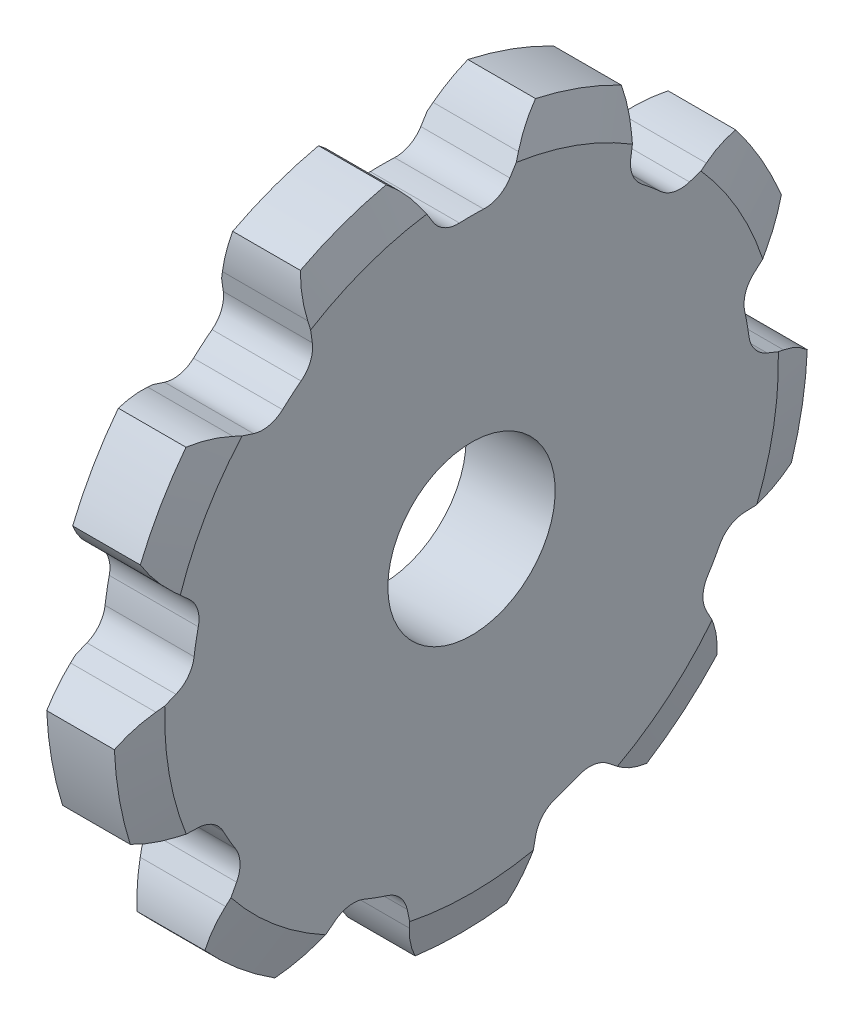
SolidWorks part; units mm, degrees
ref_plane "Plane1" through (0, 0, 0) normal (0, 0, 1) x (1, 0, 0)
ref_plane "Plane2" through (0, 0, 0) normal (0, 1, 0) x (1, 0, 0)
ref_plane "Plane3" through (0, 0, 0) normal (1, 0, 0) x (0, 0, -1)
sketch "Clipboard" plane through (0, 0, 0) normal (0, 1, 0) x (1, 0, 0)
  line L0 (0, 0) -> (65.4527, -10.3667)
  line L1 (-15, 0) -> (100, 0) construction
  line L2 (0, 0) -> (-2.1039, 2.3779)
  line L3 (0, 0) -> (-11.863, 4.5341)
  line L4 (0, 0) -> (8.5297, 1.351)
  line L5 (0, 0) -> (-71.3958, -26.6285)
  line L6 (0, 0) -> (-22.4032, -15.1155)
  line L7 (-2.1039, 2.3779) -> (14.2981, 76.7917)
  line L8 (-76.2, 54.61) -> (-19.7358, 54.61)
  line L9 (-66.6514, 23.5599) -> (-55.7196, 25.8835)
  line L10 (-76.2, 71.12) -> (20.6782, 71.12)
  line L11 (0, 0) -> (-28.448, 0)
  line L12 (-76.2, 101.6) -> (-47.752, 101.6)
  circle A0 centre (0, 0) radius 11.176
  circle A1 centre (0, 0) radius 25.4
  circle A2 centre (0, 0) radius 25.4
  dimension "Num_teeth" = 9
  dimension "Pitch_radius" = 96.8782
  dimension "Width" = 28.448
  dimension "F" = 28.448
  dimension "H" = 11.176
  dimension "Thickness" = 27.0256
sketch "BasProSke" plane through (0, 0, 0) normal (0, 1, 0) x (1, 0, 0)
  line L0 (-10, 0) -> (60, 0) construction
  line L1 (0, 0) -> (0, 93.1564)
  line L2 (0, 0) -> (27.0256, 0)
  line L3 (27.0256, 0) -> (27.0256, 93.1564)
  line L4 (23.7825, 105.2597) -> (3.2431, 105.2597)
  line L5 (0, 93.1564) -> (3.2431, 105.2597)
  line L6 (27.0256, 93.1564) -> (23.7825, 105.2597)
  dimension "Thickness" = 27.0256
  dimension "Diameter" = 210.5195
  dimension "D1" = 15
  dimension "D2" = 15
revolve "Base-Revolve" add sketch "BasProSke" angle 360 about L0
sketch "TooCutSke" plane through (0, 0, 0) normal (1, 0, 0) x (0, 0, -1)
  line L0 (-11.6391, 89.0554) -> (-14.7996, 94.1133)
  line L1 (0, 0) -> (0, 107) construction
  line L2 (3.3134, 0) -> (3.3134, 129.2389) construction
  line L3 (11.6391, 89.0554) -> (14.7996, 94.1133)
  line L4 (39.8732, 109.5507) -> (44.2168, 121.4848)
  line L5 (3.3134, 101.2907) -> (51.8809, 70.9424) construction
  line L6 (-39.8732, 109.5507) -> (-44.2168, 121.4848)
  arc A0 (3.6705, 84.8609) -> (-3.6705, 84.8609) centre (0, 0) ccw
  arc A1 (3.6705, 84.8609) -> (11.6391, 89.0554) centre (4.0569, 93.7933) ccw
  arc A2 (-3.6705, 84.8609) -> (-11.6391, 89.0554) centre (-4.0569, 93.7933) cw
  circle A3 centre (0, 0) radius 96.8782 construction
  circle A4 centre (3.3134, 96.8215) radius 11.176 construction
  arc A5 (14.7996, 94.1133) -> (39.8732, 109.5507) centre (42.8991, 76.5548) cw
  arc A6 (-14.7996, 94.1133) -> (-39.8732, 109.5507) centre (-42.8991, 76.5548) ccw
  arc A7 (44.2168, 121.4848) -> (-44.2168, 121.4848) centre (0, 0) ccw
  dimension "Pitch_radius" = 96.8782
  dimension "R" = 8.9408
  dimension "H" = 11.176
  dimension "Ag" = 64
  dimension "Angle" = 40
extrude "ToothCut" cut sketch "TooCutSke" along normal through all
pattern_circular "TeethCuts" count 9 every 40 about axis through (-10, 0, 0) along (1, 0, 0) of "ToothCut"
sketch "HubNeaOneSke" plane through (0, 0, 0) normal (-1, 0, 0) x (0, 0, 1)
  circle A0 centre (0, 0) radius 25.4
  dimension "Diameter" = 50.8
extrude "HubNearOne" [suppressed] add sketch "HubNeaOneSke" along normal blind 49.1745
sketch "HubNeaBotSke" plane through (0, 0, 0) normal (-1, 0, 0) x (0, 0, 1)
  circle A0 centre (0, 0) radius 25.4
  dimension "Diameter" = 50.8
extrude "HubNearBoth" [suppressed] add sketch "HubNeaBotSke" along normal blind 24.5872
ref_plane "FarPln" through (27.0256, 0, 0) normal (1, 0, 0) x (0, 0, -1)
sketch "HubFarSke" plane through (27.0256, 0, 0) normal (1, 0, 0) x (0, 0, -1)
  circle A0 centre (0, 0) radius 25.4
  dimension "Diameter" = 50.8
extrude "HubFar" [suppressed] add sketch "HubFarSke" along normal blind 24.5872
sketch "BorSke" plane through (0, 0, 0) normal (1, 0, 0) x (0, 0, -1)
  circle A0 centre (0, 0) radius 25.4
  dimension "Diameter" = 50.8
extrude "Bore" cut sketch "BorSke" along normal mid plane 152.4001
sketch "KeySke" plane through (0, 0, 0) normal (1, 0, 0) x (0, 0, -1)
  line L0 (-6.35, 0) -> (-6.35, 31.0642)
  line L1 (-6.35, 31.0642) -> (6.35, 31.0642)
  line L2 (6.35, 31.0642) -> (6.35, 0)
  line L3 (0, 0) -> (0, 34) construction
  line L4 (-6.35, 0) -> (6.35, 0)
  dimension "Width" = 12.7
extrude "Keyway" [suppressed] cut sketch "KeySke" along normal mid plane 152.4001
pattern_circular "Keyway2" [suppressed] count 2 every 90 about axis through (-10, 0, 0) along (1, 0, 0)
equation "\"Thickness@Clipboard\" = \"Width@Clipboard\" * 0.95"
equation "\"H@Clipboard\" = \"Diameter@Clipboard\" / 2.0"
equation "\"OAL@Clipboard\" = \"Thickness@Clipboard\""
equation "\"Pitch_radius@Clipboard\" = ( \"Pitch@Clipboard\" / 2.0) / sin(3.14159265 / \"Num_teeth@Clipboard\" )"
equation "\"MHD@Clipboard\" = (1.0 / tan(3.14159265 / \"Num_teeth@Clipboard\" ) - 0.05) * \"Pitch@Clipboard\" - \"F@Clipboard\""
equation "\"MHD@Clipboard\" = ((sgn( \"MHD@Clipboard\" - \"Hub_dia@Clipboard\" )-1)*( \"MHD@Clipboard\" - \"Hub_dia@Clipboard\" ))/-2+ \"Hub_dia@Clipboard\""
equation "\"OAL@Clipboard\" = ((sgn( \"OAL@Clipboard\" - \"Overall_len@Clipboard\" )+1)*( \"OAL@Clipboard\" - \"Overall_len@Clipboard\" ))/2 + \"Overall_len@Clipboard\" + 0.000002"
equation "\"Num_teeth@TeethCuts\" = int( \"Show_teeth@Clipboard\" ) + 1"
equation "\"Num_teeth@TeethCuts\" = ((sgn( \"Num_teeth@TeethCuts\" - \"Num_teeth@Clipboard\" )-1)*( \"Num_teeth@TeethCuts\" - \"Num_teeth@Clipboard\" ))/-2+ \"Num_teeth@Clipboard\""
equation "\"Num_teeth@TeethCuts\" = ((sgn( \"Num_teeth@TeethCuts\" - 2.0)+1)*( \"Num_teeth@TeethCuts\" - 2.0))/2 +2.0"
equation "\"Angle@TeethCuts\" = 360.0 / \"Num_teeth@Clipboard\""
equation "\"Pitch_radius@TooCutSke\" = \"Pitch_radius@Clipboard\""
equation "\"Cp@TooCutSke\" = 0.05 * \"Pitch@Clipboard\""
equation "\"Rt@TooCutSke\" = 0.5 * \"Pitch@Clipboard\""
equation "\"R@TooCutSke\"  = 0.8 * \"H@Clipboard\""
equation "\"Db@TooCutSke\" = \"Pitch_radius@Clipboard\" - \"H@Clipboard\" - 0.03"
equation "\"Ag@TooCutSke\" =  2.0 * \"Ap@Clipboard\" + 360.0 / \"Num_teeth@Clipboard\""
equation "\"H@TooCutSke\" = \"H@Clipboard\""
equation "\"Angle@TooCutSke\" =  360.0 / \"Num_teeth@Clipboard\""
equation "\"Wf@TooCutSke\" = 0.01 * \"Pitch@Clipboard\" * \"Num_teeth@Clipboard\""
equation "\"Wf@TooCutSke\" = ((sgn( \"Wf@TooCutSke\" - \"H@Clipboard\" * 0.8 )-1)*( \"Wf@TooCutSke\" - \"H@Clipboard\" * 0.8 ))/-2+ \"H@Clipboard\" * 0.8"
equation "\"Diameter@BasProSke\" = (1.0 / tan(3.14159265 / \"Num_teeth@Clipboard\" )) * \"Pitch@Clipboard\" + \"F@Clipboard\""
equation "\"Thickness@BasProSke\"  = \"Thickness@Clipboard\""
equation "\"G1@BasProSke\" =  \"Thickness@Clipboard\" * 0.12"
equation "\"G2@BasProSke\" =   \"Thickness@Clipboard\" * 0.12"
equation "\"MHD@Clipboard\" = ((sgn( \"MHD@Clipboard\" - \"Db@TooCutSke\" * 2.0  )-1)*( \"MHD@Clipboard\" - \"Db@TooCutSke\" * 2.0 ))/-2+ \"Db@TooCutSke\" * 2.0"
equation "\"Diameter@HubNeaOneSke\" = \"MHD@Clipboard\""
equation "\"Length@HubNearOne\" = \"OAL@Clipboard\" - \"Thickness@BasProSke\""
equation "\"Diameter@HubNeaBotSke\" = \"MHD@Clipboard\""
equation "\"Length@HubNearBoth\" = ( \"OAL@Clipboard\" - \"Thickness@BasProSke\" ) / 2.0"
equation "\"Thickness@FarPln\" = \"Thickness@BasProSke\""
equation "\"Diameter@HubFarSke\" = \"MHD@Clipboard\""
equation "\"Length@HubFar\" = ( \"OAL@Clipboard\" - \"Thickness@BasProSke\" ) / 2.0"
equation "\"D1@Bore\" = \"OAL@Clipboard\" * 2.0"
equation "\"D1@Keyway\" = \"OAL@Clipboard\" * 2.0"
equation "\"Offset@KeySke\" = \"T_dim@Clipboard\" - \"Diameter@BorSke\" / 2.0"
